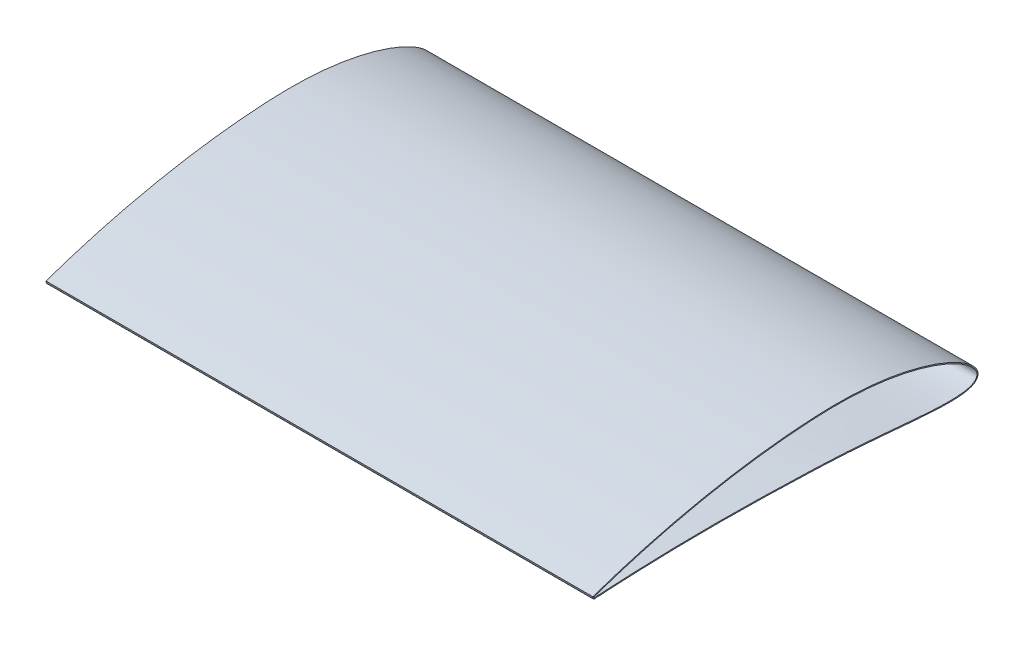
SolidWorks part; units mm, degrees
other "Markup1"
sketch "Sketch2" plane through (-254, -8.3615, 356.0294) normal (-0.9998, -0.003, 0.0177) x (0.0176, 0.0231, 0.9996)
material "E-Glass Fiber"
ref_plane "Front Plane" through (0, 0, 0) normal (0, 0, 1) x (1, 0, 0)
ref_plane "Top Plane" through (0, 0, 0) normal (0, 1, 0) x (1, 0, 0)
ref_plane "Right Plane" through (0, 0, 0) normal (1, 0, 0) x (0, 0, -1)
curve "Curve1"
  spline degree 3 poles (0, 0.0012, 1.0003) (0, 0.0015, 0.9994) (0, 0.0028, 0.9958) (0, 0.0055, 0.9879) (0, 0.0099, 0.9747) (0, 0.0159, 0.9565) (0, 0.0233, 0.9333) (0, 0.0318, 0.9054) (0, 0.0411, 0.8731) (0, 0.051, 0.8366) (0, 0.0612, 0.7964) (0, 0.0713, 0.7528) (0, 0.0811, 0.7063) (0, 0.0903, 0.6574) (0, 0.0985, 0.6067) (0, 0.1057, 0.5546) (0, 0.1115, 0.5018) (0, 0.1158, 0.4488) (0, 0.1186, 0.3959) (0, 0.1189, 0.3436) (0, 0.1164, 0.2927) (0, 0.1112, 0.2442) (0, 0.1037, 0.1988) (0, 0.0942, 0.157) (0, 0.0831, 0.1194) (0, 0.0711, 0.0865) (0, 0.0584, 0.0585) (0, 0.0457, 0.0357) (0, 0.0334, 0.0184) (0, 0.0218, 0.0064) (0, 0.0108, -0.0005) (0, -0.0003, -0.0011) (0, -0.0092, 0.0055) (0, -0.0148, 0.017) (0, -0.0185, 0.0329) (0, -0.0204, 0.0533) (0, -0.0208, 0.0781) (0, -0.0198, 0.107) (0, -0.0176, 0.1398) (0, -0.0147, 0.176) (0, -0.0111, 0.2153) (0, -0.0074, 0.2574) (0, -0.0037, 0.3019) (0, -0.0005, 0.3484) (0, 0.002, 0.397) (0, 0.0037, 0.4471) (0, 0.0055, 0.4983) (0, 0.0069, 0.5496) (0, 0.0079, 0.6006) (0, 0.0085, 0.6505) (0, 0.0086, 0.699) (0, 0.0083, 0.7455) (0, 0.0076, 0.7894) (0, 0.0065, 0.8302) (0, 0.0053, 0.8675) (0, 0.0039, 0.9007) (0, 0.0027, 0.9296) (0, 0.0013, 0.9539) (0, 0.0006, 0.9727) (0, -0.0011, 0.9872) (0, 0, 0.9944) (0, -0.002, 0.9999) (0, -0.0005, 1) (0, 0, 1) knots 0 0 0 0 0.001372 0.005465 0.012235 0.021602 0.033461 0.047671 0.064081 0.082496 0.102719 0.124527 0.147676 0.171913 0.196978 0.222597 0.248497 0.274385 0.300041 0.32569 0.350525 0.37428 0.396711 0.417577 0.436654 0.453744 0.46868 0.481329 0.491631 0.499616 0.505546 0.510185 0.514824 0.520702 0.528516 0.538466 0.550543 0.564643 0.580638 0.598345 0.617584 0.638174 0.659922 0.682632 0.706121 0.730727 0.7557 0.780732 0.805564 0.829932 0.85357 0.876213 0.89761 0.917519 0.935698 0.951943 0.966047 0.97784 0.987174 0.993932 0.998018 0.999386 1 1 1 1
sketch "Sketch1" plane through (0, 0, 0) normal (1, 0, 0) x (0, 0, -1)
  line L0 (-354.7873, -0.0303) -> (-354.8762, 0.4104)
  line L1 (-354.7873, -0.0303) -> (0.8093, 1.5275) construction
  line L2 (0.8093, 1.5275) -> (0.7921, 5.4415) construction
  line L3 (-355.7813, -0.16) -> (-356.0294, 1.0708)
  spline S0 degree 1 poles (-356.0294, 1.0708) (-355.7813, -0.16) knots 0 0 1 1 construction
  spline S1 degree 3 poles (-354.8762, 0.4104) (-354.5599, 0.5194) (-353.2997, 0.9536) (-350.4787, 1.9271) (-345.801, 3.4978) (-336.0241, 6.7216) (-319.6545, 11.7989) (-300.5983, 17.1306) (-282.4229, 21.7243) (-261.1758, 26.6516) (-238.6223, 31.1455) (-208.7748, 36.0048) (-183.9617, 39.0905) (-158.9023, 41.1132) (-140.0967, 42.1114) (-121.5167, 42.2289) (-103.4222, 41.3211) (-86.1884, 39.4787) (-70.0435, 36.8105) (-55.1998, 33.4329) (-41.8434, 29.5109) (-30.1305, 25.2201) (-20.187, 20.7343) (-12.1072, 16.2263) (-5.9269, 11.8553) (-1.6792, 7.7165) (0.7658, 3.7968) (0.9875, -0.1483) (-1.3511, -3.3089) (-5.4508, -5.2881) (-11.0873, -6.5875) (-18.3491, -7.2685) (-27.1638, -7.4049) (-37.4471, -7.0538) (-49.0831, -6.3019) (-61.9524, -5.238) (-75.9299, -3.9839) (-96.4067, -2.1536) (-117.9372, -0.4584) (-140.4848, 0.6745) (-158.2965, 1.2867) (-176.4839, 1.9179) (-200.672, 2.5862) (-224.5411, 2.9791) (-247.8302, 3.0285) (-264.3373, 2.9074) (-279.9331, 2.6564) (-294.438, 2.2829) (-307.6819, 1.8521) (-319.5134, 1.3711) (-329.7674, 0.9129) (-338.3889, 0.4268) (-345.077, 0.1915) (-350.2276, -0.4064) (-352.7802, -0.0354) (-354.7446, -0.7581) (-354.7772, -0.2025) (-354.7873, -0.0303) knots 0 0 0 0 0.001372 0.005465 0.012235 0.021602 0.047671 0.082496 0.102719 0.124527 0.171913 0.196978 0.248497 0.274385 0.300041 0.32569 0.350525 0.37428 0.396711 0.417577 0.436654 0.453744 0.46868 0.481329 0.491631 0.499616 0.505546 0.510185 0.514824 0.520702 0.528516 0.538466 0.550543 0.564643 0.580638 0.598345 0.617584 0.638174 0.682632 0.706121 0.730727 0.7557 0.780732 0.829932 0.85357 0.876213 0.89761 0.917519 0.935698 0.951943 0.966047 0.97784 0.987174 0.993932 0.998018 0.999386 1 1 1 1
  spline S2 degree 3 poles (-356.0294, 1.0708) (-348.8068, 3.5591) (-334.3137, 8.3987) (-305.0227, 17.1398) (-267.9722, 26.5042) (-230.4397, 33.7217) (-200.1876, 38.1139) (-177.3993, 40.6676) (-154.5431, 42.4484) (-131.6073, 43.3755) (-108.6332, 42.7966) (-89.5704, 40.9369) (-74.434, 38.5689) (-63.1626, 36.3176) (-52.0007, 33.5569) (-40.9837, 30.2424) (-31.9663, 26.9597) (-24.8924, 23.9577) (-19.678, 21.4886) (-14.5784, 18.7674) (-9.6365, 15.7331) (-5.7201, 12.8485) (-2.8041, 10.2108) (-0.8097, 7.9993) (0.9536, 5.4706) (1.8267, 2.8505) (1.8287, 0.5804) (1.3439, -1.1087) (0.4339, -2.5446) (-1.1152, -4.1337) (-3.4092, -5.4544) (-6.2413, -6.4463) (-9.1163, -7.1407) (-12.9596, -7.769) (-17.7821, -8.1875) (-23.5483, -8.3615) (-29.3027, -8.3178) (-35.0455, -8.1273) (-40.7762, -7.8324) (-48.4067, -7.3387) (-57.9264, -6.5844) (-69.3333, -5.5826) (-80.7332, -4.5557) (-92.1313, -3.5515) (-107.3326, -2.2957) (-126.3437, -0.9632) (-145.3831, -0.1511) (-160.6352, 0.3667) (-175.8853, 0.8944) (-194.9456, 1.4407) (-217.8243, 1.8769) (-236.8904, 2.025) (-252.1434, 1.9977) (-263.5829, 1.9042) (-275.0214, 1.7404) (-286.4576, 1.4951) (-295.9876, 1.2274) (-303.6097, 0.9813) (-309.3259, 0.7769) (-315.0428, 0.5518) (-320.7576, 0.3113) (-326.4654, 0.0596) (-331.2293, -0.1801) (-335.0499, -0.3834) (-337.9104, -0.5288) (-340.7518, -0.6489) (-343.1033, -0.7582) (-345.0032, -0.8822) (-346.443, -1.005) (-347.9246, -1.1411) (-349.3933, -1.2404) (-350.6256, -1.2477) (-351.5127, -1.1926) (-352.1109, -1.176) (-352.6084, -1.2069) (-353.0416, -1.2775) (-353.3273, -1.3432) (-353.5861, -1.418) (-353.834, -1.4893) (-354.1253, -1.5551) (-354.4896, -1.5941) (-354.9528, -1.5235) (-355.3731, -1.2467) (-355.6868, -0.8168) (-355.7586, -0.4226) (-355.7748, -0.2607) (-355.7813, -0.16) knots -0.001196 -0.001196 -0.001196 -0.001196 0.030089 0.061374 0.123944 0.186514 0.217798 0.249083 0.280368 0.311653 0.342938 0.374223 0.389866 0.405508 0.421151 0.436793 0.452436 0.460257 0.468078 0.475899 0.483721 0.491542 0.495452 0.499363 0.503274 0.507184 0.50914 0.511095 0.51305 0.515005 0.518916 0.522827 0.526737 0.530648 0.538469 0.54629 0.554112 0.561933 0.569754 0.577575 0.593218 0.60886 0.624503 0.640145 0.655788 0.687073 0.718358 0.734 0.749643 0.780928 0.812212 0.843497 0.85914 0.874782 0.890425 0.906067 0.92171 0.929531 0.937352 0.945174 0.952995 0.960816 0.968637 0.972548 0.976458 0.980369 0.98428 0.986235 0.98819 0.990146 0.992101 0.994056 0.995034 0.996012 0.996989 0.997478 0.997967 0.998211 0.998456 0.9987 0.998945 0.999189 0.999311 0.999433 0.999678 0.999922 0.999922 0.999922 0.999922
  dimension "D1" = 355.6
  dimension "D2" = 1
extrude "Boss-Extrude1" add sketch "Sketch1" along normal blind 254 and the other way blind 254
